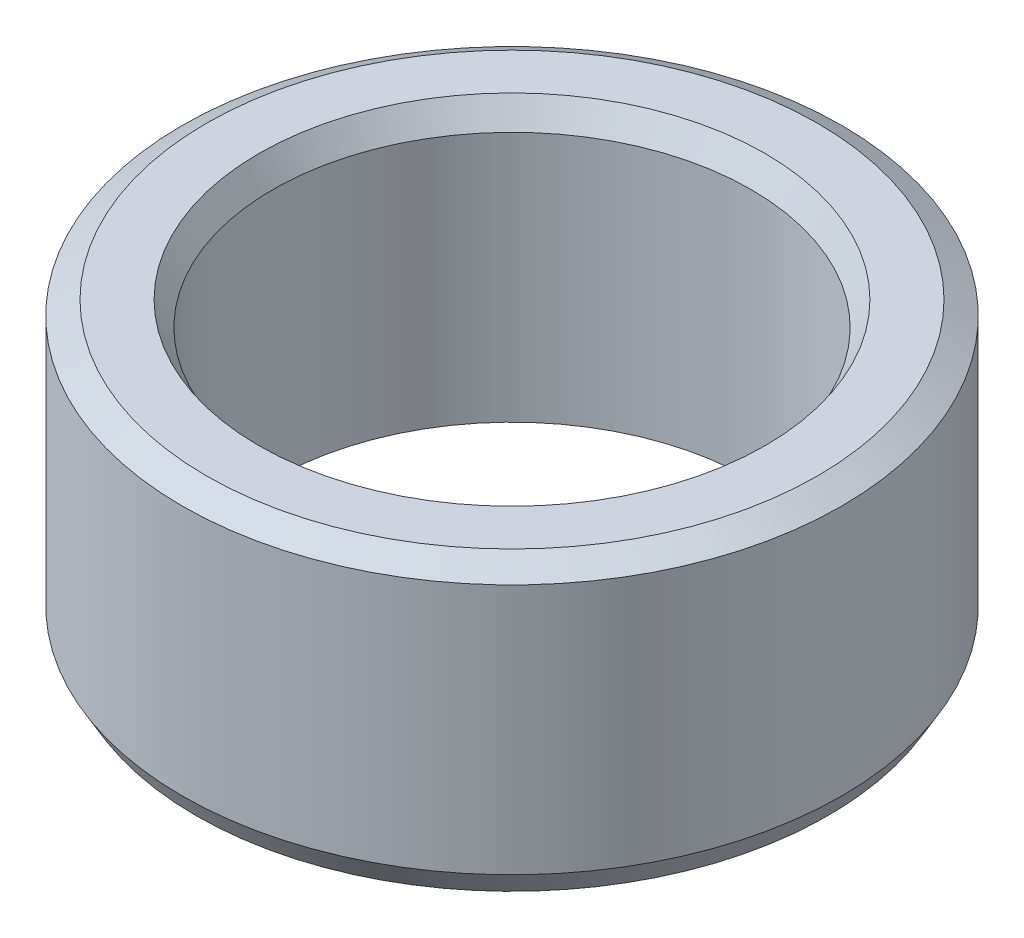
SolidWorks part; units mm, degrees
ref_plane "Front Plane" through (0, 0, 0) normal (0, 0, 1) x (1, 0, 0)
ref_plane "Top Plane" through (0, 0, 0) normal (0, 1, 0) x (1, 0, 0)
ref_plane "Right Plane" through (0, 0, 0) normal (1, 0, 0) x (0, 0, -1)
sketch "Sketch1" plane through (0, 0, 0) normal (0, 1, 0) x (1, 0, 0)
  circle A0 centre (0, 0) radius 12.5
  dimension "SLEEVE_OD" = 25
extrude "Boss-Extrude1" add sketch "Sketch1" along normal blind 10.9656
sketch "Sketch2" plane through (0, 0, 0) normal (0, 1, 0) x (1, 0, 0)
  circle A0 centre (0, 0) radius 9.0659
  dimension "BORE_D" = 18.1319
extrude "Cut-Extrude1" cut sketch "Sketch2" along normal through all
chamfer "Chamfer1" distance 0.53 angle 60 4 edges at (0, 10.9656, 9.0659) (0, 0, 9.0659) (0, 0, 12.5) (0, 10.9656, 12.5) first distance on face at (0, 10.9656, 9.0659) first distance on face at (0, 0, 9.0659) first distance on face at (0, 10.9656, 12.5)
